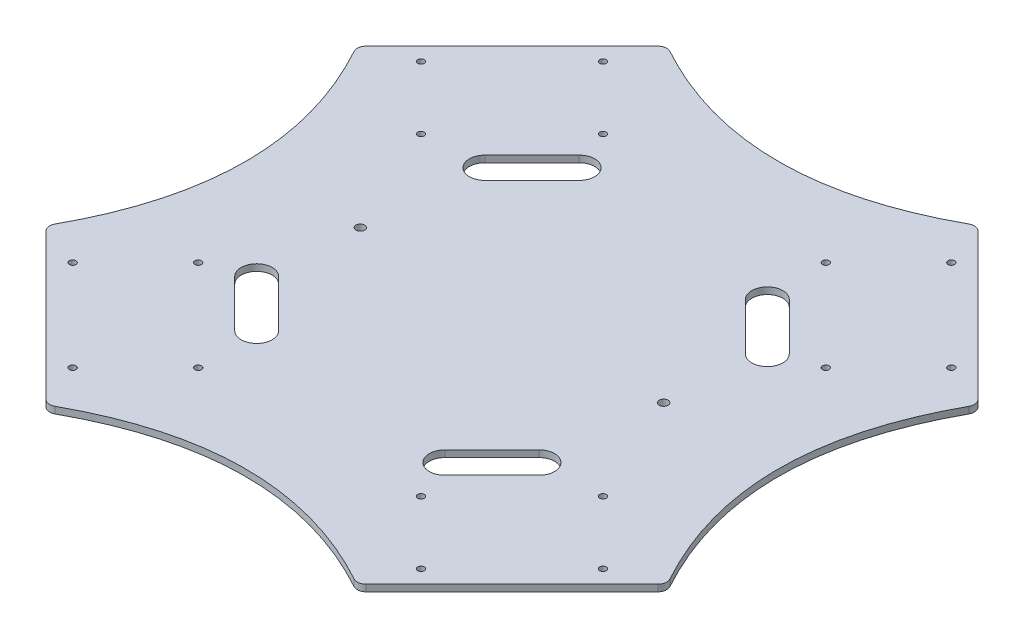
SolidWorks part; units mm, degrees
material "EM-CF"
ref_plane "Płaszczyzna przednia" through (0, 0, 0) normal (0, 0, 1) x (1, 0, 0)
ref_plane "Płaszczyzna górna" through (0, 0, 0) normal (0, 1, 0) x (1, 0, 0)
ref_plane "Płaszczyzna prawa" through (0, 0, 0) normal (1, 0, 0) x (0, 0, -1)
sketch "Szkic1" plane through (0, 0, 0) normal (0, 1, 0) x (1, 0, 0)
  line L0 (0, 0) -> (0, -120) construction
  line L1 (0, -120) -> (0, -140) construction
  line L2 (-70, -140) -> (70, -140) construction
  line L3 (0, 0) -> (-120, 0) construction
  line L4 (-120, 0) -> (-140, 0) construction
  line L5 (-140, 70) -> (-140, -70) construction
  line L6 (0, 0) -> (0, 120) construction
  line L7 (0, 120) -> (0, 140) construction
  line L8 (70, 140) -> (-70, 140) construction
  line L9 (0, 0) -> (120, 0) construction
  line L10 (120, 0) -> (140, 0) construction
  line L11 (140, -70) -> (140, 70) construction
  line L12 (-70, -140) -> (-140, -70)
  line L14 (70, -140) -> (140, -70)
  line L16 (140, 70) -> (70, 140)
  line L17 (-70, 140) -> (-140, 70)
  spline S0 degree 2 poles (-70, -140) (0, -100) (70, -140) knots 0 0 0 1 1 1
  spline S1 degree 2 poles (-140, 70) (-100, 0) (-140, -70) knots 0 0 0 1 1 1
  spline S2 degree 2 poles (70, 140) (0, 100) (-70, 140) knots 0 0 0 1 1 1
  spline S3 degree 2 poles (140, -70) (100, 0) (140, 70) knots 0 0 0 1 1 1
  point P7 (0, -140)
  point P14 (-140, 0)
  point P20 (0, 140)
  point P26 (140, 0)
  point P28 (0, 0)
  dimension "D1" = 120
  dimension "D2" = 20
  dimension "D3" = 140
extrude "Dodanie-wyciągnięcie1" add sketch "Szkic1" along normal blind 3
fillet "Zaokrąglenie1" radius 4 8 edges at (-140, 1.5, -70) (-70, 1.5, -140) (70, 1.5, -140) (140, 1.5, -70) (140, 1.5, 70) (70, 1.5, 140) (-140, 1.5, 70) (-70, 1.5, 140)
sketch "Szkic2" plane through (0, 3, 0) normal (0, 1, 0) x (1, 0, 0)
  line L0 (0, 0) -> (-70.7107, -70.7107) construction
  line L1 (-120.2082, -49.4975) -> (-49.4975, -120.2082) construction
  line L2 (-70.7107, -70.7107) -> (-98.9949, -98.9949) construction
  line L3 (-78.4889, -119.501) -> (-119.501, -78.4889) construction
  circle A0 centre (-78.4889, -119.501) radius 1.5
  circle A1 centre (-119.501, -78.4889) radius 1.5
  circle A2 centre (-50.2046, -91.2168) radius 1.5
  circle A3 centre (-91.2168, -50.2046) radius 1.5
  point P6 (-70.7107, -70.7107)
  point P10 (-98.9949, -98.9949)
  point P13 (-84.8528, -84.8528)
  point P16 (-84.8528, -84.8528)
  dimension "D5" = 3
  dimension "D1" = 100
  dimension "D3" = 40
extrude "Wytnij-wyciągnięcie1" cut sketch "Szkic2" against normal through all
ref_axis "Oś1" through (0, -82.2794, 0) along (0, 1, 0)
pattern_circular "Szyk kołowy1" count 4 every 90 about axis through (0, -82.2794, 0) along (0, 1, 0) of "Wytnij-wyciągnięcie1"
sketch "Szkic3" plane through (0, 3, 0) normal (0, 1, 0) x (1, 0, 0)
  line L0 (3.5562, 5.4754) -> (-53.0123, 62.0439) construction
  line L1 (-42.4057, 72.6505) -> (-63.6189, 51.4373)
  line L2 (-63.6189, 51.4373) -> (-42.4057, 72.6505) construction
  line L3 (-68.5687, 56.3871) -> (-47.3554, 77.6003)
  line L4 (-58.6692, 46.4876) -> (-37.456, 67.7008)
  arc A0 (-68.5687, 56.3871) -> (-58.6692, 46.4876) centre (-63.6189, 51.4373) ccw
  arc A1 (-37.456, 67.7008) -> (-47.3554, 77.6003) centre (-42.4057, 72.6505) ccw
  point P2 (-53.0123, 62.0439)
  point P5 (-53.0123, 62.0439)
  dimension "D1" = 80
  dimension "D2" = 30
  dimension "D3" = 14
extrude "Wytnij-wyciągnięcie2" cut sketch "Szkic3" against normal up to next contours L4 A1 L3 A0 region at (-57.6099, 3, -66.6416)
pattern_circular "Szyk kołowy2" count 4 every 90 about axis through (0, -82.2794, 0) along (0, 1, 0) of "Wytnij-wyciągnięcie2"
sketch "Szkic4" plane through (0, 3, 0) normal (0, 1, 0) x (1, 0, 0)
  line L0 (68.34, 0) -> (-68.34, 0) construction
  circle A0 centre (-68.34, 0) radius 2
  circle A1 centre (68.34, 0) radius 2
  point P3 (0, 0)
  dimension "D2" = 4
  dimension "D3" = 4
  dimension "D1" = 136.68
extrude "Wytnij-wyciągnięcie3" cut sketch "Szkic4" against normal up to next
